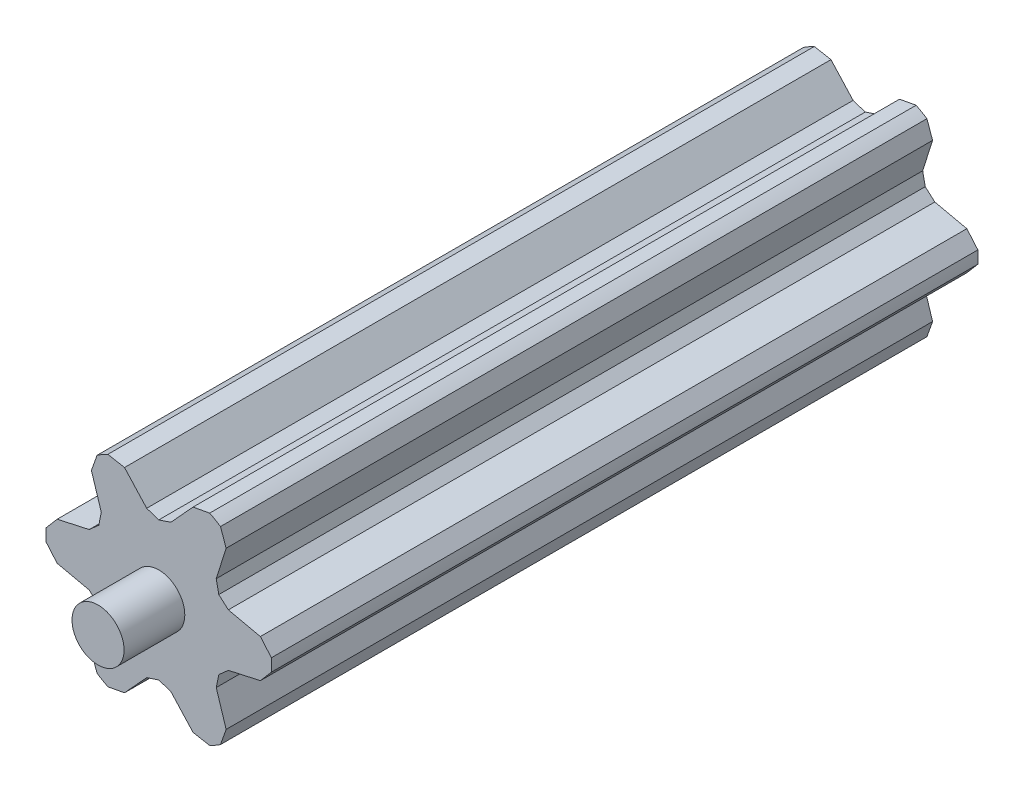
SolidWorks part; units mm, degrees
ref_plane "Front Plane" through (0, 0, 0) normal (0, 0, 1) x (1, 0, 0)
ref_plane "Top Plane" through (0, 0, 0) normal (0, 1, 0) x (1, 0, 0)
ref_plane "Right Plane" through (0, 0, 0) normal (1, 0, 0) x (0, 0, -1)
sketch "Sketch1" plane through (0, 0, 0) normal (0, 0, 1) x (1, 0, 0)
  line L1 (1.2374, -1.2374) -> (-1.2374, -1.2374) construction
  line L2 (1.2374, -1.2374) -> (1.2374, 1.2374) construction
  line L3 (1.2374, 1.2374) -> (-1.2374, 1.2374) construction
  line L4 (-1.2374, -1.2374) -> (-1.2374, 1.2374) construction
  line L5 (1.2374, -1.2374) -> (-1.2374, 1.2374) construction
  line L6 (1.2374, 1.2374) -> (-1.2374, -1.2374) construction
  circle A0 centre (0, 0) radius 6.5
  circle A1 centre (0, 0) radius 1.75 construction
  dimension "D1" = 13
  dimension "D2" = 3.5
extrude "Boss-Extrude1" add sketch "Sketch1" along normal blind 40.71
sketch "Sketch2" plane through (0, 0, 0) normal (0, 0, 1) x (1, 0, 0)
  line L0 (0, 0) -> (0, 10.088) construction
  line L1 (0, 3.994) -> (-0.6978, 4.226)
  line L8 (-3.4668, 8.7118) -> (0, 10.6127)
  line L11 (-0.6978, 4.226) -> (-1.9741, 5.6218)
  line L12 (-1.9741, 5.6218) -> (-2.934, 5.8001)
  line L13 (-2.934, 5.8001) -> (-3.4668, 8.7118)
  line L14 (2.934, 5.8001) -> (3.4668, 8.7118)
  line L15 (1.9741, 5.6218) -> (2.934, 5.8001)
  line L16 (0.6978, 4.226) -> (1.9741, 5.6218)
  line L17 (3.4668, 8.7118) -> (0, 10.6127)
  line L18 (0, 3.994) -> (0.6978, 4.226)
  circle A14 centre (0, 0) radius 6.5 construction
  point P4 (0, 3.994)
  point P16 (0, 6.5)
  point P17 (-1.4007, 4.9784)
  point P18 (-2.2581, 6.4762)
  point P19 (-2.522, 6.4621)
  point P20 (-0.6978, 4.226)
  point P21 (-1.7159, 5.9542)
  point P22 (-2.8653, 6.9311)
  point P23 (-3.4668, 8.7118)
  point P24 (0, 10.6127)
  point P25 (-2.934, 5.8001)
  point P26 (-1.9741, 5.6218)
extrude "Cut-Extrude1" cut sketch "Sketch2" along normal through all
pattern_circular "CirPattern1" count 6 over 360 about axis through (0, 0, 40.71) along (0, 0, -1) of "Cut-Extrude1" reverse direction yes
sketch "Sketch3" plane through (0, 0, 0) normal (0, 0, 1) x (1, 0, 0)
  circle A0 centre (0, 0) radius 7.5
  dimension "D1" = 15
sketch "Sketch4" plane through (0, 0, 40.71) normal (0, 0, 1) x (1, 0, 0)
  circle A0 centre (0, 0) radius 1.5
  dimension "D1" = 3
extrude "Boss-Extrude2" add sketch "Sketch4" along normal blind 3.5
sketch "Sketch5" plane through (0, 0, 0) normal (0, 0, 1) x (1, 0, 0)
  circle A0 centre (0, 0) radius 1.6
  dimension "D1" = 3.2
extrude "Cut-Extrude2" cut sketch "Sketch5" along normal blind 15
